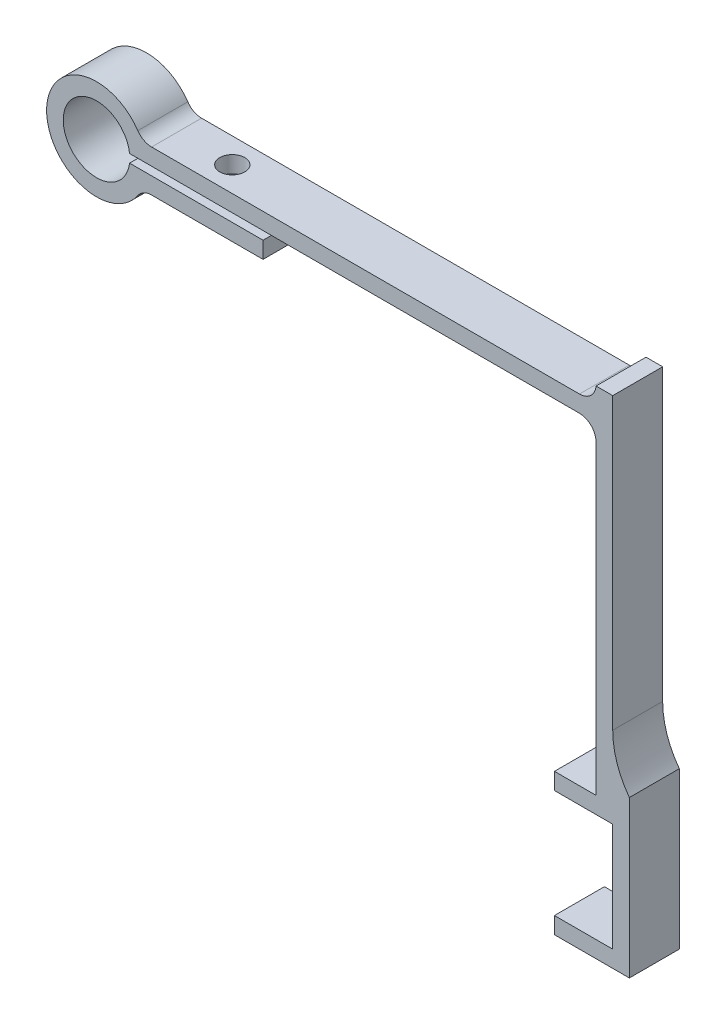
SolidWorks part; units mm, degrees
ref_plane "Front Plane" through (0, 0, 0) normal (0, 0, 1) x (1, 0, 0)
ref_plane "Top Plane" through (0, 0, 0) normal (0, 1, 0) x (1, 0, 0)
ref_plane "Right Plane" through (0, 0, 0) normal (1, 0, 0) x (0, 0, -1)
sketch "Sketch1" plane through (0, 0, 0) normal (0, 0, 1) x (1, 0, 0)
  line L0 (4.9749, 0.5) -> (9.5271, 0.5)
  line L1 (4.9749, -0.5) -> (20, -0.5)
  line L2 (4.9749, 0.5) -> (3.9686, 0.5)
  line L3 (4.9749, -0.5) -> (3.9686, -0.5)
  line L4 (20, -2.5) -> (5.4544, -2.5)
  line L5 (20, -2.5) -> (20, -0.5)
  line L6 (9.5271, 0.5) -> (60, 0.5)
  line L7 (60, 0.5) -> (60, -40.25)
  line L8 (60, -40.25) -> (62, -40.25)
  line L9 (62, -40.25) -> (62, 4.3312)
  line L12 (60, 2.5) -> (5.4544, 2.5)
  line L13 (62, 4.3312) -> (60, 4.3312)
  line L14 (60, 4.3312) -> (60, 2.5)
  arc A0 (5.4544, 2.5) -> (5.4544, -2.5) centre (0, 0) ccw
  arc A1 (3.9686, 0.5) -> (3.9686, -0.5) centre (0, 0) ccw
  dimension "D3" = 6
  dimension "D4" = 8
  dimension "D6" = 2
  dimension "D8" = 62
  dimension "D11" = 20
  dimension "D1" = 0.5
  dimension "D2" = 0.5
  dimension "D5" = 2
  dimension "D7" = 2
  dimension "D9" = 40.25
  dimension "D10" = 2
extrude "Boss-Extrude1" add sketch "Sketch1" along normal blind 6
fillet "Fillet1" radius 2 4 edges at (5.4544, 2.5, 3) (5.4544, -2.5, 3) (60, 2.5, 3) (60, 0.5, 3)
sketch "Sketch2" plane through (0, -2.5, 0) normal (0, -1, 0) x (1, 0, 0)
  line L0 (6.6144, 6) -> (20, 6) construction
  circle A0 centre (13.3072, 3) radius 1.5
  dimension "D1" = 3
  dimension "D2" = 3
extrude "Cut-Extrude1" cut sketch "Sketch2" against normal blind 10
sketch "Sketch3" plane through (62, 0, 0) normal (1, 0, 0) x (0, 0, -1)
  line L0 (-6, -40.25) -> (-6, 4.3312) construction
  line L1 (-6, -36.4757) -> (0, -36.4757)
  line L2 (-6, -36.4757) -> (-6, -55.25)
  line L3 (-6, -55.25) -> (0, -55.25)
  line L4 (0, -36.4757) -> (0, -55.25)
  line L5 (-6, -40.25) -> (0, -40.25) construction
  dimension "D1" = 18.7743
  dimension "D2" = 15
extrude "Boss-Extrude2" add sketch "Sketch3" along normal blind 2
fillet "Fillet2" radius 10 1 edges at (62, -36.4757, 3)
sketch "Sketch4" plane through (60, 0, 0) normal (-1, 0, 0) x (0, 0, 1)
  line L0 (6, -1.5) -> (6, -40.25) construction
  line L1 (0, -40.25) -> (6, -40.25)
  line L2 (0, -40.25) -> (0, -38.25)
  line L3 (0, -38.25) -> (6, -38.25)
  line L4 (6, -40.25) -> (6, -38.25)
  dimension "D1" = 2
extrude "Boss-Extrude3" add sketch "Sketch4" along normal blind 5
sketch "Sketch5" plane through (62, 0, 0) normal (-1, 0, 0) x (0, 0, 1)
  line L0 (6, -40.25) -> (6, -55.25) construction
  line L1 (0, -55.25) -> (6, -55.25)
  line L2 (0, -55.25) -> (0, -53.25)
  line L3 (0, -53.25) -> (6, -53.25)
  line L4 (6, -55.25) -> (6, -53.25)
  dimension "D1" = 2
extrude "Boss-Extrude4" add sketch "Sketch5" along normal up to surface (7 mm away) up to face at (55, -39.25, 3)
